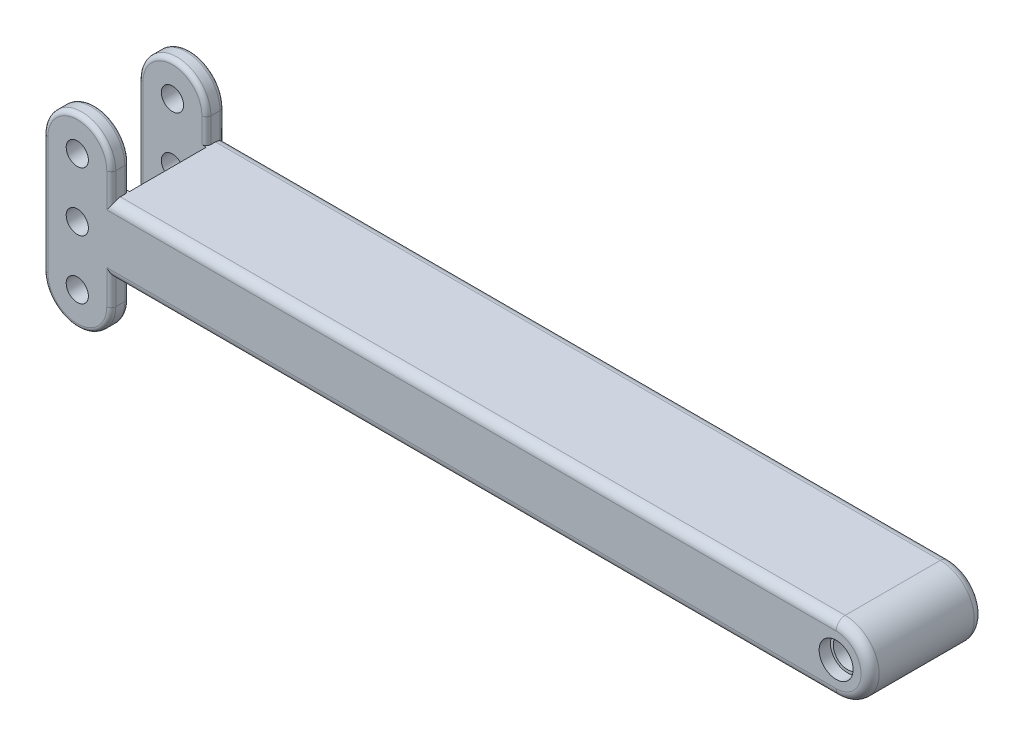
SolidWorks part; units mm, degrees
ref_plane "Front Plane" through (0, 0, 0) normal (0, 0, 1) x (1, 0, 0)
ref_plane "Top Plane" through (0, 0, 0) normal (0, 1, 0) x (1, 0, 0)
ref_plane "Right Plane" through (0, 0, 0) normal (1, 0, 0) x (0, 0, -1)
sketch "Sketch1" plane through (0, 0, 0) normal (0, 0, 1) x (1, 0, 0)
  line L0 (0, 0) -> (0, 33.02) construction
  line L1 (-9.525, 0) -> (-9.525, 33.02)
  line L2 (9.525, 0) -> (9.525, 33.02)
  line L3 (9.525, 26.035) -> (212.725, 26.035)
  line L4 (9.525, 6.985) -> (212.725, 6.985)
  line L5 (0, 16.51) -> (9.525, 26.035) construction
  line L6 (0, 16.51) -> (9.525, 6.985) construction
  arc A0 (-9.525, 0) -> (9.525, 0) centre (0, 0) ccw
  arc A1 (9.525, 33.02) -> (-9.525, 33.02) centre (0, 33.02) ccw
  arc A2 (212.725, 26.035) -> (212.725, 6.985) centre (212.725, 16.51) cw
  circle A3 centre (0, 33.02) radius 3.1115
  circle A4 centre (0, 0) radius 3.1115
  circle A5 centre (0, 16.51) radius 3.1115
  circle A6 centre (212.725, 16.51) radius 3.9687
  point P3 (0, 16.51)
  point P17 (9.525, 16.51)
  dimension "D1" = 9.525
  dimension "D5" = 6.223
  dimension "D4" = 6.223
  dimension "D7" = 7.9375
  dimension "D2" = 33.02
  dimension "D3" = 19.05
  dimension "D6" = 203.2
extrude "Boss-Extrude1" add sketch "Sketch1" along normal blind 31.75 contours A2 L3 L2 L4 | L2 A1 L1 A0 A4 A3 region at (-8.9705, 16.51, 0) region at (113.6547, 16.51, 0)
sketch "Sketch2" plane through (-9.525, 0, 0) normal (-1, 0, 0) x (0, 0, 1)
  line L0 (0, 0) -> (0, -9.525) construction
  line L1 (0, 0) -> (31.75, 0) construction
  line L2 (31.75, -9.525) -> (31.75, 0) construction
  line L3 (0, 42.545) -> (0, 33.02) construction
  line L4 (31.75, 33.02) -> (31.75, 42.545) construction
  line L5 (31.75, 33.02) -> (0, 33.02) construction
  line L6 (0, 33.02) -> (0, 0) construction
  line L7 (31.75, 0) -> (31.75, 33.02) construction
  line L8 (0, 0) -> (0, -9.525)
  line L9 (0, 0) -> (31.75, 0)
  line L10 (31.75, -9.525) -> (31.75, 0)
  line L11 (0, 42.545) -> (0, 33.02)
  line L12 (31.75, 33.02) -> (31.75, 42.545)
  line L13 (31.75, 33.02) -> (0, 33.02)
  line L14 (0, 33.02) -> (0, 0)
  line L15 (31.75, 0) -> (31.75, 33.02)
  line L16 (31.75, 42.545) -> (0, 42.545) construction
  line L17 (5.08, 42.545) -> (26.67, 42.545)
  line L18 (5.08, 42.545) -> (5.08, -9.525)
  line L19 (5.08, -9.525) -> (26.67, -9.525)
  line L20 (26.67, 42.545) -> (26.67, -9.525)
  line L21 (0, -9.525) -> (31.75, -9.525) construction
  line L26 (15.875, 0) -> (15.875, 50000) construction
  point P20 (15.875, 42.545)
  point P29 (15.875, 0)
  line M7 (0, 0) -> (31.75, 0)
  line M9 (31.75, 33.02) -> (0, 33.02)
  dimension "D1" = 21.59
extrude "Cut-Extrude1" cut sketch "Sketch2" against normal blind 19.05 contours L9 L26 L18 M9 | L26 L20 L13 M7 | L26 L17 L18 M9 | L26 L13 L20 L17 | L19 L26 L9 L18 | L26 L19 L20 M7 region at (-9.525, 16.51, 10.4775) region at (-9.525, -4.7625, 15.875) region at (-9.525, 16.51, 21.2725) region at (-9.525, 37.7825, 10.4775) region at (-9.525, 37.7825, 21.2725)
fillet "Fillet1" radius 2.54 6 edges at (111.125, 26.035, 0) (222.25, 16.51, 0) (111.125, 26.035, 31.75) (222.25, 16.51, 31.75) (111.125, 6.985, 0) (111.125, 6.985, 31.75)
fillet "Fillet2" radius 1.27 20 edges at (9.525, 3.4925, 26.67) (9.525, 29.5275, 26.67) (0, 42.545, 26.67) (-9.525, 16.51, 26.67) (9.525, 28.2575, 0) (0, 42.545, 0) (-9.525, 16.51, 0) (9.525, 4.7625, 0) (9.525, 3.4925, 5.08) (9.525, 29.5275, 5.08) (0, 42.545, 5.08) (-9.525, 16.51, 5.08) (9.525, 28.2575, 31.75) (0, 42.545, 31.75) (-9.525, 16.51, 31.75) (9.525, 4.7625, 31.75) (0, -9.525, 26.67) (0, -9.525, 0) (0, -9.525, 5.08) (0, -9.525, 31.75)
sketch "Sketch3" plane through (0, 0, 31.75) normal (0, 0, 1) x (1, 0, 0)
  circle A0 centre (212.725, 16.51) radius 3.9687 construction
  circle A1 centre (212.725, 16.51) radius 3.9687
  circle A2 centre (212.725, 16.51) radius 4.7625
  dimension "D1" = 9.525
extrude "Cut-Extrude2" cut sketch "Sketch3" against normal blind 3.175
ref_plane "Plane1" through (0, 0, 15.875) normal (0, 0, 1) x (1, 0, 0)
mirror "Mirror1" about plane through (0, 0, 15.875) normal (0, 0, 1) of "Cut-Extrude2"
